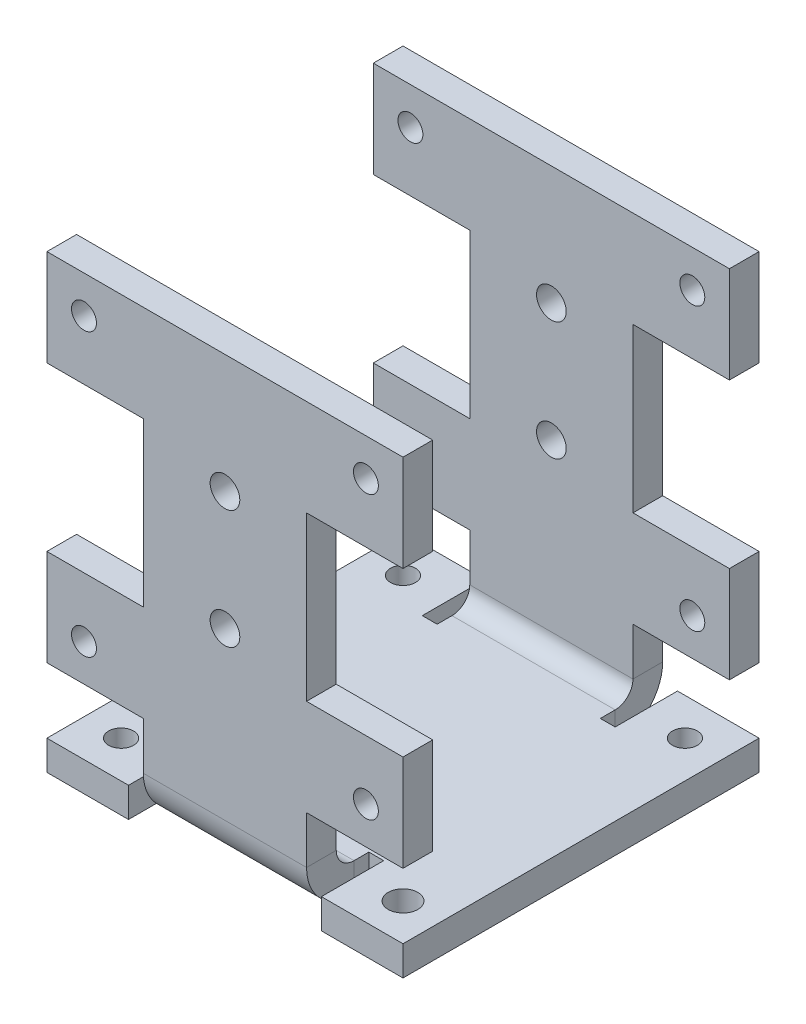
SolidWorks part; units mm, degrees
note: The reader was unsure of these and kept them because the rebuilt part matched: flange length of "边线-法兰1", "边线-法兰2".
ref_plane "前视基准面" through (0, 0, 0) normal (0, 0, 1) x (1, 0, 0)
ref_plane "上视基准面" through (0, 0, 0) normal (0, 1, 0) x (1, 0, 0)
ref_plane "右视基准面" through (0, 0, 0) normal (1, 0, 0) x (0, 0, -1)
other "Configuration Table"
sketch "草图16" plane through (0, 0, 0) normal (0, 1, 0) x (1, 0, 0)
  line L0 (16.25, 30) -> (30, 30)
  line L5 (-30, -30) -> (-16.25, -30)
  line L6 (-30, -30) -> (-30, 30)
  line L11 (-30, 30) -> (-16.25, 30)
  line L12 (30, -30) -> (30, 30)
  line L17 (-30, -30) -> (30, 30) construction
  line L18 (-30, 30) -> (30, -30) construction
  line L19 (23.75, 23.75) -> (-23.75, 23.75) construction
  line L20 (23.75, 23.75) -> (23.75, -23.75) construction
  line L21 (23.75, -23.75) -> (-23.75, -23.75) construction
  line L22 (-23.75, 23.75) -> (-23.75, -23.75) construction
  line L23 (23.75, 23.75) -> (-23.75, -23.75) construction
  line L24 (23.75, -23.75) -> (-23.75, 23.75) construction
  line L26 (-16.25, 30) -> (-16.25, 23.75) construction
  line L27 (-16.25, 23.75) -> (16.25, 23.75) construction
  line L28 (16.25, 30) -> (16.25, 23.75) construction
  line L29 (-16.25, -23.75) -> (16.25, -23.75) construction
  line L30 (-16.25, -23.75) -> (-16.25, -30) construction
  line L32 (16.25, -23.75) -> (16.25, -30) construction
  line L33 (16.25, -30) -> (30, -30)
  line L34 (-16.25, -25) -> (-16.25, -30)
  line L35 (-16.25, -25) -> (16.25, -25)
  line L36 (-16.25, -25) -> (-16.25, 25) construction
  line L37 (-16.25, 25) -> (16.25, 25)
  line L38 (16.25, -25) -> (16.25, 25) construction
  line L39 (-16.25, -25) -> (16.25, 25) construction
  line L40 (-16.25, 25) -> (16.25, -25) construction
  line L41 (16.25, -25) -> (16.25, -30)
  line L42 (-16.25, 30) -> (-16.25, 25)
  line L43 (16.25, 30) -> (16.25, 25)
  circle A0 centre (-23.75, 23.75) radius 2.1
  circle A1 centre (-23.75, -23.75) radius 2.1
  circle A2 centre (-23.75, 23.75) radius 4.25 construction
  circle A3 centre (-23.75, -23.75) radius 4.25 construction
  circle A4 centre (23.75, 23.75) radius 2.1
  circle A5 centre (23.75, 23.75) radius 4.25 construction
  circle A6 centre (23.75, -23.75) radius 2.5
  circle A7 centre (23.75, -23.75) radius 2.1 construction
  point P0 (0, 0)
  point P6 (0, 0)
  point P23 (0, 0)
  point P24 (0, 23.75)
  point P29 (0, -23.75)
  dimension "D4" = 4.2
  dimension "D5" = 4.2
  dimension "D6" = 8.5
  dimension "D7" = 8.5
  dimension "D8" = 4.2
  dimension "D9" = 8.5
  dimension "D10" = 5
  dimension "D11" = 4.2
  dimension "D1" = 60
  dimension "D2" = 60
  dimension "D3" = 47.5
  dimension "D12" = 32.5
  dimension "D13" = 32.5
  dimension "D14" = 50
base flange "基体-法兰2" sketch "草图16" thickness 5 reverse thickness direction no parameters "D1"=0.7366
edge flange "边线-法兰1" sketch "草图19" flange angle 90 flange length 76 flange position material outside bend radius 3 thickness 5 relief rectangular parameters "D6"=10
sketch "草图19" plane through (0, 0, 25) normal (0, 0, 1) x (1, 0, 0)
  line L5 (-16.25, 0) -> (16.25, 0) construction
  line L6 (-13.75, 0) -> (13.75, 0)
  line L7 (-13.75, 0) -> (-13.75, 71)
  line L8 (-13.75, 71) -> (13.75, 71)
  line L9 (13.75, 0) -> (13.75, 71)
  point P6 (0, 0)
  dimension "D1" = 27.5
  dimension "D2" = 71
bend "边线折弯1" bend radius 3 bend angle 90 parameters "D5"=1
edge flange "边线-法兰2" sketch "草图22" flange angle 90 flange length 76 flange position material outside bend radius 3 thickness 5 relief rectangular parameters "D6"=10
sketch "草图22" plane through (0, 0, -25) normal (0, 0, -1) x (-1, 0, 0)
  line L6 (-13.75, 71) -> (13.75, 71)
  line L7 (-13.75, 71) -> (-13.75, 0)
  line L8 (-13.75, 0) -> (13.75, 0)
  line L9 (13.75, 71) -> (13.75, 0)
bend "边线折弯2" bend radius 3 bend angle 90 parameters "D5"=2
sketch "草图23" plane through (0, 0, 0) normal (0, 0, 1) x (1, 0, 0)
  line L0 (13.75, 71) -> (-13.75, 71) construction
  line L1 (-30, 71) -> (30, 71) construction
  line L2 (-30, 71) -> (-30, 11) construction
  line L3 (-30, 11) -> (30, 11) construction
  line L4 (30, 71) -> (30, 11) construction
  line L5 (-13.75, 71) -> (-13.75, 3) construction
  line L6 (-30, 71) -> (-13.75, 71)
  line L7 (-30, 71) -> (-30, 54.75)
  line L8 (-30, 54.75) -> (-13.75, 54.75)
  line L9 (-13.75, 71) -> (-13.75, 54.75)
  line L10 (13.75, 3) -> (13.75, 71) construction
  line L11 (13.75, 71) -> (30, 71)
  line L12 (13.75, 71) -> (13.75, 54.75)
  line L13 (13.75, 54.75) -> (30, 54.75)
  line L14 (30, 71) -> (30, 54.75)
  line L15 (30, 11) -> (13.75, 11)
  line L16 (30, 11) -> (30, 27.25)
  line L17 (30, 27.25) -> (13.75, 27.25)
  line L18 (13.75, 11) -> (13.75, 27.25)
  line L20 (-30, 11) -> (-13.75, 11)
  line L21 (-30, 11) -> (-30, 27.25)
  line L22 (-30, 27.25) -> (-13.75, 27.25)
  line L23 (-13.75, 11) -> (-13.75, 27.25)
  point P6 (0, 71)
  dimension "D1" = 60
  dimension "D2" = 60
  dimension "D3" = 16.25
  dimension "D4" = 16.25
extrude "凸台-拉伸1" add sketch "草图23" against normal up to surface (5 mm away) from surface at 30 up to face at (0, 37, 25) starting at face at (0, 37, 30)
sketch "草图24" plane through (0, 0, 0) normal (0, 0, 1) x (1, 0, 0)
  line L4 (30, 71) -> (13.75, 71)
  line L5 (30, 54.75) -> (30, 71)
  line L6 (13.75, 54.75) -> (30, 54.75)
  line L7 (13.75, 71) -> (13.75, 54.75)
  line L8 (30, 71) -> (13.75, 71)
  line L9 (30, 54.75) -> (30, 71)
  line L10 (13.75, 54.75) -> (30, 54.75)
  line L11 (13.75, 71) -> (13.75, 54.75)
  line L12 (-13.75, 71) -> (-30, 71)
  line L13 (-13.75, 54.75) -> (-13.75, 71)
  line L14 (-30, 54.75) -> (-13.75, 54.75)
  line L15 (-30, 71) -> (-30, 54.75)
  line L16 (-13.75, 71) -> (-30, 71)
  line L17 (-13.75, 54.75) -> (-13.75, 71)
  line L18 (-30, 54.75) -> (-13.75, 54.75)
  line L19 (-30, 71) -> (-30, 54.75)
  line L20 (-30, 11) -> (-13.75, 11)
  line L21 (-30, 27.25) -> (-30, 11)
  line L22 (-13.75, 27.25) -> (-30, 27.25)
  line L23 (-13.75, 11) -> (-13.75, 27.25)
  line L24 (-30, 11) -> (-13.75, 11)
  line L25 (-30, 27.25) -> (-30, 11)
  line L26 (-13.75, 27.25) -> (-30, 27.25)
  line L27 (-13.75, 11) -> (-13.75, 27.25)
  line L28 (13.75, 11) -> (30, 11)
  line L29 (30, 11) -> (30, 27.25)
  line L30 (30, 27.25) -> (13.75, 27.25)
  line L31 (13.75, 27.25) -> (13.75, 11)
  line L32 (13.75, 11) -> (30, 11)
  line L33 (30, 11) -> (30, 27.25)
  line L34 (30, 27.25) -> (13.75, 27.25)
  line L35 (13.75, 27.25) -> (13.75, 11)
  dimension "D1" = 0
  dimension "D2" = 0
  dimension "D3" = 0
  dimension "D4" = 0
extrude "凸台-拉伸2" add sketch "草图24" against normal up to surface (5 mm away) from surface at -25 up to face at (0, 37, -30) starting at face at (0, 37, -25)
sketch "草图25" plane through (0, 0, 0) normal (0, 0, 1) x (1, 0, 0)
  line L0 (-30, 71) -> (30, 11) construction
  line L1 (-30, 71) -> (30, 71) construction
  line L2 (-30, 71) -> (-30, 11) construction
  line L3 (-30, 11) -> (30, 11) construction
  line L4 (30, 71) -> (30, 11) construction
  line L5 (30, 71) -> (-30, 11) construction
  line L7 (-23.75, 17.25) -> (23.75, 17.25) construction
  line L8 (-23.75, 17.25) -> (-23.75, 64.75) construction
  line L9 (-23.75, 64.75) -> (23.75, 64.75) construction
  line L10 (23.75, 17.25) -> (23.75, 64.75) construction
  line L11 (-23.75, 17.25) -> (23.75, 64.75) construction
  line L12 (-23.75, 64.75) -> (23.75, 17.25) construction
  circle A0 centre (-23.75, 64.75) radius 2.1
  circle A1 centre (23.75, 64.75) radius 2.1
  circle A2 centre (-23.75, 17.25) radius 2.1
  circle A3 centre (23.75, 17.25) radius 2.1
  point P6 (0, 41)
  dimension "D2" = 4.2
  dimension "D3" = 4.2
  dimension "D4" = 4.2
  dimension "D5" = 4.2
  dimension "D1" = 47.5
extrude "切除-拉伸1" cut sketch "草图25" against normal through all and the other way through all normal cut yes
sketch "草图26" plane through (0, 0, 0) normal (0, 0, 1) x (1, 0, 0)
  line L0 (30, 71) -> (-30, 11) construction
  line L6 (-30, 71) -> (30, 11) construction
  line L8 (0, 31) -> (0, 51) construction
  circle A2 centre (0, 51) radius 2.5
  circle A3 centre (0, 31) radius 2.5
  point P8 (0, 41)
  dimension "D2" = 5
  dimension "D3" = 5
  dimension "D1" = 20
extrude "切除-拉伸2" cut sketch "草图26" against normal through all and the other way through all normal cut yes
sketch "折弯-线3" plane through (0, 0, 0) normal (0, 1, 0) x (1, 0, 0)
sketch "边界框3" plane through (0, 0, 0) normal (0, 1, 0) x (1, 0, 0)
sheet metal parameters "钣金10" thickness 5 parameters "D1"=0.7366
flat pattern "平板型式10" [suppressed]
sketch "折弯-线4" plane through (0, 0, 0) normal (0, 1, 0) x (1, 0, 0)
sketch "边界框4" [suppressed] plane through (0, 0, 0) normal (0, 1, 0) x (1, 0, 0)
sheet metal parameters "钣金21" thickness 5 parameters "D1"=0.7366
flat pattern "平板型式10" [suppressed]
sketch "折弯-线4" plane through (0, 0, 0) normal (0, 1, 0) x (1, 0, 0)
sketch "边界框4" [suppressed] plane through (0, 0, 0) normal (0, 1, 0) x (1, 0, 0)
bend of the flat pattern "展平-<边线折弯1>1"
sheet metal parameters "钣金22" thickness 5 parameters "D1"=0.7366
flat pattern "平板型式10" [suppressed]
sketch "折弯-线4" plane through (0, 0, 0) normal (0, 1, 0) x (1, 0, 0)
sketch "边界框4" [suppressed] plane through (0, 0, 0) normal (0, 1, 0) x (1, 0, 0)
bend of the flat pattern "展平-<边线折弯1>1"
bend of the flat pattern "展平-<边线折弯2>1"
sheet metal parameters "钣金23" thickness 5 parameters "D1"=0.7366
flat pattern "平板型式10" [suppressed]
sketch "折弯-线4" plane through (0, 0, 0) normal (0, 1, 0) x (1, 0, 0)
sketch "边界框4" [suppressed] plane through (0, 0, 0) normal (0, 1, 0) x (1, 0, 0)
bend of the flat pattern "展平-<边线折弯1>1"
bend of the flat pattern "展平-<边线折弯2>1"
sheet metal parameters "钣金24" thickness 5 parameters "D1"=0.7366
flat pattern "平板型式10" [suppressed]
sketch "折弯-线4" plane through (0, 0, 0) normal (0, 1, 0) x (1, 0, 0)
sketch "边界框4" [suppressed] plane through (0, 0, 0) normal (0, 1, 0) x (1, 0, 0)
bend of the flat pattern "展平-<边线折弯1>1"
bend of the flat pattern "展平-<边线折弯2>1"
sheet metal parameters "钣金25" thickness 5 parameters "D1"=0.7366
flat pattern "平板型式10" [suppressed]
sketch "折弯-线4" plane through (0, 0, 0) normal (0, 1, 0) x (1, 0, 0)
sketch "边界框4" [suppressed] plane through (0, 0, 0) normal (0, 1, 0) x (1, 0, 0)
bend of the flat pattern "展平-<边线折弯1>1"
bend of the flat pattern "展平-<边线折弯2>1"
sheet metal parameters "钣金26" thickness 5 parameters "D1"=0.7366
flat pattern "平板型式10" [suppressed]
sketch "折弯-线4" plane through (0, 0, 0) normal (0, 1, 0) x (1, 0, 0)
sketch "边界框4" [suppressed] plane through (0, 0, 0) normal (0, 1, 0) x (1, 0, 0)
bend of the flat pattern "展平-<边线折弯1>1"
bend of the flat pattern "展平-<边线折弯2>1"
